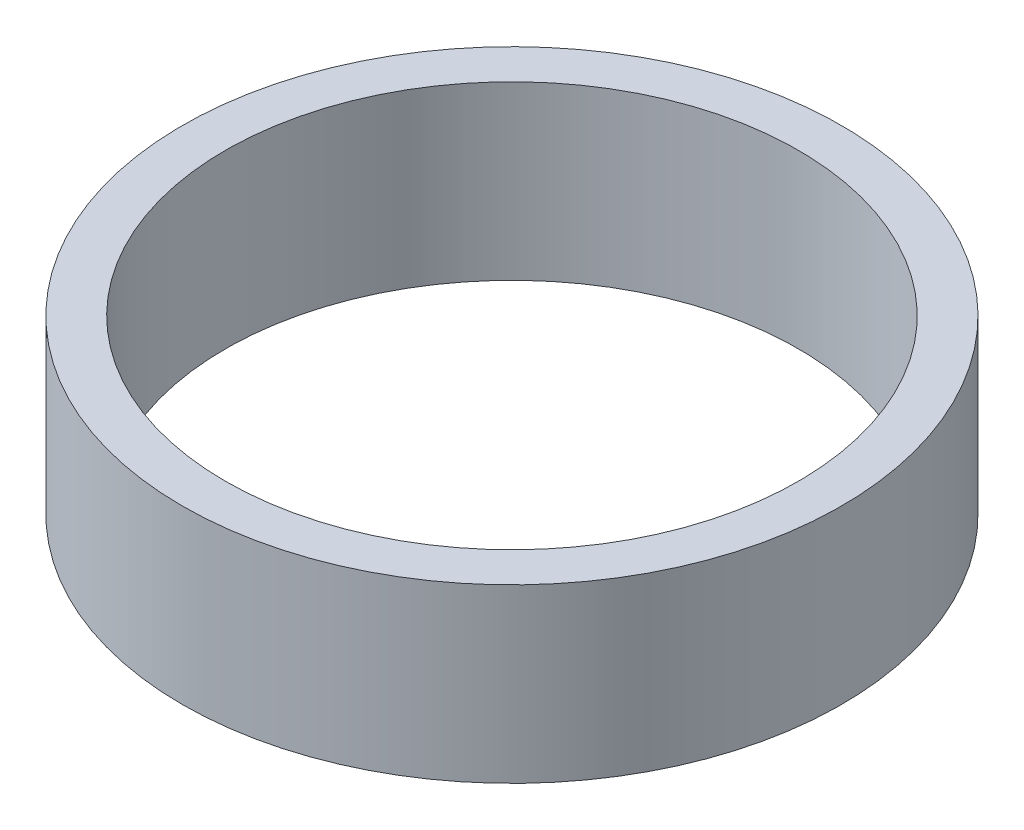
SolidWorks part; units mm, degrees
ref_plane "Front Plane" through (0, 0, 0) normal (0, 0, 1) x (1, 0, 0)
ref_plane "Top Plane" through (0, 0, 0) normal (0, 1, 0) x (1, 0, 0)
ref_plane "Right Plane" through (0, 0, 0) normal (1, 0, 0) x (0, 0, -1)
sketch "Sketch1" plane through (0, 0, 0) normal (0, 1, 0) x (1, 0, 0)
  circle A0 centre (0, 0) radius 57.5
  dimension "FLANGE_OD" = 115
extrude "Boss-Extrude1" add sketch "Sketch1" along normal blind 30
sketch "Sketch2" plane through (0, 0, 0) normal (0, 1, 0) x (1, 0, 0)
  circle A0 centre (0, 0) radius 50
  dimension "BORE_D" = 100
extrude "Cut-Extrude1" cut sketch "Sketch2" along normal through all
sketch "Sketch3" plane through (0, 30, 0) normal (0, 1, 0) x (1, 0, 0)
  circle A0 centre (0, 0) radius 26.7174 construction
  circle A1 centre (-26.7174, 0) radius 1.5
  dimension "BOLT_D" = 3
  dimension "BOLT_PCD" = 53.4347
extrude "Cut-Extrude2" cut sketch "Sketch3" against normal blind 18.5879 rebuild error yes
pattern_circular "CirPattern1" count 8 over 360 rebuild error yes
